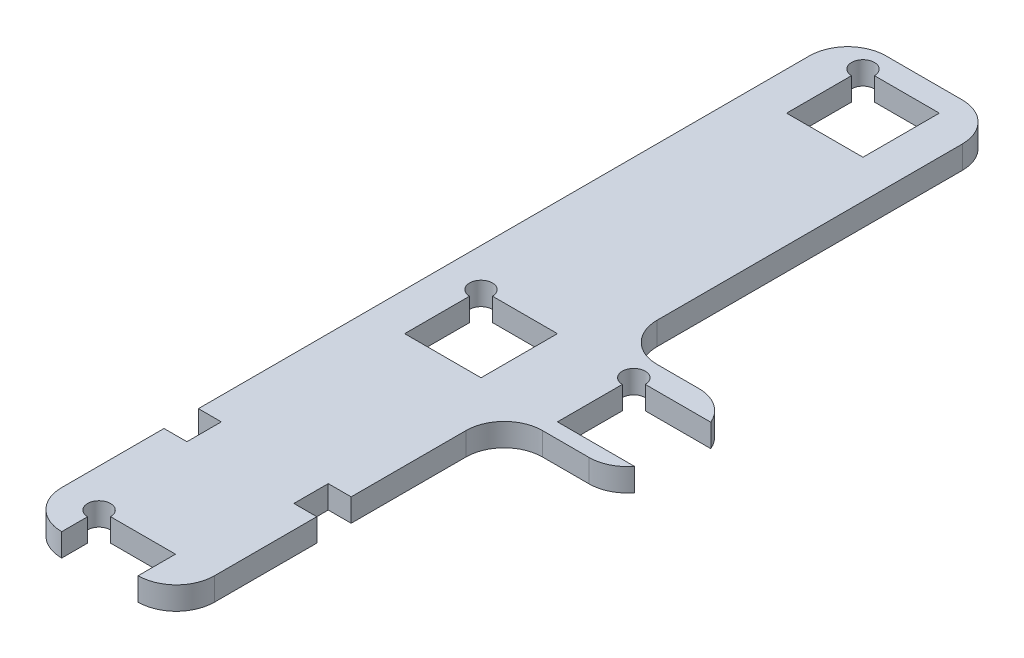
SolidWorks part; units mm, degrees
ref_plane "Front Plane" through (0, 0, 0) normal (0, 0, 1) x (1, 0, 0)
ref_plane "Top Plane" through (0, 0, 0) normal (0, 1, 0) x (1, 0, 0)
ref_plane "Right Plane" through (0, 0, 0) normal (1, 0, 0) x (0, 0, -1)
sketch "Sketch1" plane through (0, 0, 0) normal (0, 1, 0) x (1, 0, 0)
  line L1 (-10, 55) -> (10, 55)
  line L2 (-10, 55) -> (-10, -55)
  line L3 (-10, -55) -> (10, -55)
  line L4 (10, 55) -> (10, -55)
  line L5 (-10, 55) -> (10, -55) construction
  line L6 (-10, -55) -> (10, 55) construction
  line L7 (-10, -50) -> (10, -50)
  line L8 (-10, -50) -> (-10, -72)
  line L9 (-10, -72) -> (10, -72)
  line L10 (10, -50) -> (10, -72)
  line L11 (-10, -50) -> (10, -72) construction
  line L12 (-10, -72) -> (10, -50) construction
  line L13 (-10, -64.5) -> (-7, -64.5)
  line L14 (-10, -64.5) -> (-10, -69)
  line L15 (-10, -69) -> (-7, -69)
  line L16 (-7, -64.5) -> (-7, -69)
  line L17 (-10, -64.5) -> (-7, -69) construction
  line L18 (-10, -69) -> (-7, -64.5) construction
  line L19 (7, -64.5) -> (10, -64.5)
  line L20 (7, -64.5) -> (7, -69)
  line L21 (7, -69) -> (10, -69)
  line L22 (10, -64.5) -> (10, -69)
  line L23 (7, -64.5) -> (10, -69) construction
  line L24 (7, -69) -> (10, -64.5) construction
  line L25 (-10, -30) -> (-7, -30)
  line L26 (-10, -30) -> (-10, -34.5)
  line L27 (-10, -34.5) -> (-7, -34.5)
  line L28 (-7, -30) -> (-7, -34.5)
  line L29 (-10, -30) -> (-7, -34.5) construction
  line L30 (-10, -34.5) -> (-7, -30) construction
  line L31 (7, -30) -> (10, -30)
  line L32 (7, -30) -> (7, -34.5)
  line L33 (7, -34.5) -> (10, -34.5)
  line L34 (10, -30) -> (10, -34.5)
  line L35 (7, -30) -> (10, -34.5) construction
  line L36 (7, -34.5) -> (10, -30) construction
  circle A0 centre (-5, 52) radius 1.5
  circle A1 centre (-5, 2) radius 1.5
  circle A2 centre (-5, -48) radius 1.5
  point P0 (0, 0)
  point P12 (-8.5, -66.75)
  point P13 (0, -61)
  point P15 (0, -50)
  point P23 (8.5, -66.75)
  point P28 (-8.5, -32.25)
  point P33 (8.5, -32.25)
  point P38 (0, 0)
  dimension "D5" = 3
  dimension "D6" = 3
  dimension "D7" = 3
  dimension "D1" = 110
  dimension "D2" = 20
  dimension "D3" = 50
  dimension "D4" = 50
  dimension "D8" = 5
  dimension "D9" = 2
  dimension "D10" = 2
  dimension "D11" = 22
  dimension "D12" = 3
  dimension "D13" = 3
  dimension "D14" = 4.5
  dimension "D15" = 19
  dimension "D16" = 4.5
  dimension "D17" = 30
extrude "Boss-Extrude3" add sketch "Sketch1" along normal blind 3 contours L33 L32 L31 L4 L1 L2 L25 L28 L27 L7 A2 A1 A0 | L21 L20 L19 L10 L3 L8 L13 L16 L15 L9 | L7 L2 L3 L4 region at (0.0517, 0, -2.9625) region at (0, 0, 52.5) region at (0, 0, 63.2196)
fillet "Fillet2" radius 5 4 edges at (-10, 1.5, -55) (10, 1.5, -55) (-10, 1.5, 72) (10, 1.5, 72)
sketch "Sketch3" plane through (0, 3, 0) normal (0, 1, 0) x (1, 0, 0)
  line L1 (-14.3931, -52.8905) -> (14.3931, -52.8905)
  line L2 (-14.3931, -52.8905) -> (-14.3931, -73.8911)
  line L3 (-14.3931, -73.8911) -> (14.3931, -73.8911)
  line L4 (14.3931, -52.8905) -> (14.3931, -73.8911)
  line L5 (-14.3931, -52.8905) -> (14.3931, -73.8911) construction
  line L6 (-14.3931, -73.8911) -> (14.3931, -52.8905) construction
  point P0 (0, -63.3908)
extrude "Cut-Extrude1" cut sketch "Sketch3" against normal up to next
fillet "Fillet3" radius 5 2 edges at (10, 1.5, 52.8905) (-10, 1.5, 52.8905)
sketch "Sketch5" plane through (0, 3, 0) normal (0, 1, 0) x (1, 0, 0)
  line L1 (-5, -48) -> (5, -48)
  line L2 (-5, -48) -> (-5, -58)
  line L3 (-5, -58) -> (5, -58)
  line L4 (5, -48) -> (5, -58)
  line L5 (-5, -48) -> (5, -58) construction
  line L6 (-5, -58) -> (5, -48) construction
  line L13 (-5, 52) -> (5, 52)
  line L14 (-5, 52) -> (-5, 42)
  line L15 (-5, 42) -> (5, 42)
  line L16 (5, 52) -> (5, 42)
  line L17 (-5, 52) -> (5, 42) construction
  line L18 (-5, 42) -> (5, 52) construction
  circle A0 centre (-5, -48) radius 1.5 construction
  circle A2 centre (-5, 52) radius 1.5 construction
  point P0 (0, -53)
  point P5 (0, 0)
  point P14 (0, 47)
  point P19 (0, 0)
  dimension "D1" = 10
  dimension "D2" = 10
  dimension "D5" = 10
  dimension "D6" = 10
extrude "Cut-Extrude2" cut sketch "Sketch5" against normal blind 10
sketch "Sketch8" plane through (0, 3, 0) normal (0, 1, 0) x (1, 0, 0)
  line L1 (-9.92, 5.0378) -> (25.08, 5.0378)
  line L2 (-9.92, 5.0378) -> (-9.92, -9.9622)
  line L3 (-9.92, -9.9622) -> (25.08, -9.9622)
  line L4 (25.08, 5.0378) -> (25.08, -9.9622)
  line L5 (-9.92, 5.0378) -> (25.08, -9.9622) construction
  line L6 (-9.92, -9.9622) -> (25.08, 5.0378) construction
  circle A0 centre (15, 2) radius 1.5
  circle A1 centre (-5, 2) radius 1.5 construction
  circle A2 centre (-5, 2) radius 1.5
  point P0 (7.58, -2.4622)
  dimension "D4" = 3
  dimension "D5" = 20
  dimension "D1" = 15
  dimension "D2" = 35
  dimension "D3" = 2
extrude "Boss-Extrude5" add sketch "Sketch8" against normal blind 3 contours L2 L1 L4 L3 | A0 | A2
sketch "Sketch9" plane through (0, 3, 0) normal (0, 1, 0) x (1, 0, 0)
  line L1 (-5, 2) -> (5, 2)
  line L2 (-5, 2) -> (-5, -8)
  line L3 (-5, -8) -> (5, -8)
  line L4 (5, 2) -> (5, -8)
  line L5 (-5, 2) -> (5, -8) construction
  line L6 (-5, -8) -> (5, 2) construction
  line L7 (15, 2) -> (26, 2)
  line L8 (15, 2) -> (15, -8)
  line L9 (15, -8) -> (26, -8)
  line L10 (26, 2) -> (26, -8)
  line L11 (15, 2) -> (26, -8) construction
  line L12 (15, -8) -> (26, 2) construction
  circle A0 centre (-5, 2) radius 1.5 construction
  circle A1 centre (15, 2) radius 1.5 construction
  point P0 (0, -3)
  point P5 (20.5, -3)
  point P10 (0, 0)
  point P13 (0, 0)
  dimension "D1" = 10
  dimension "D2" = 10
  dimension "D3" = 10
  dimension "D4" = 11
extrude "Cut-Extrude3" cut sketch "Sketch9" against normal up to next
fillet "Fillet4" radius 5 4 edges at (10, 1.5, 9.9622) (25.08, 1.5, 9.9622) (25.08, 1.5, -5.0378) (10, 1.5, -5.0378)
